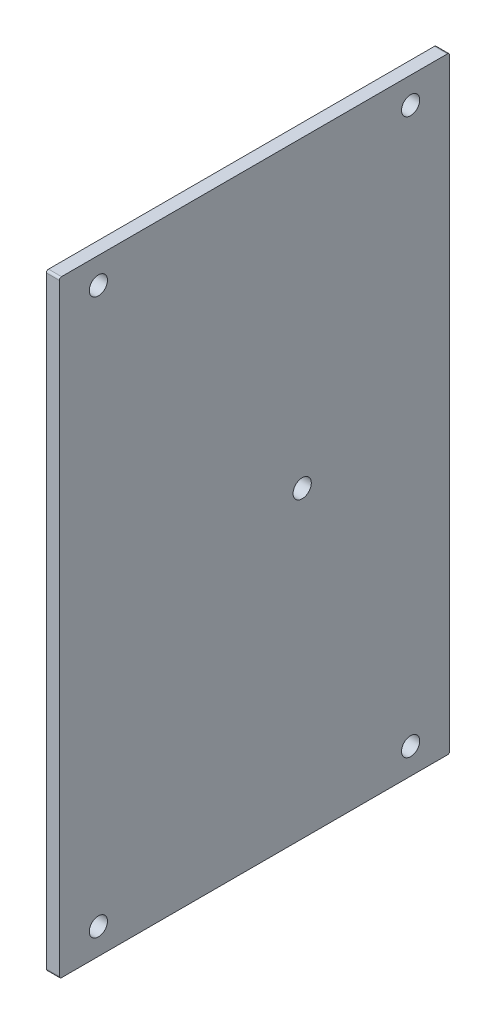
SolidWorks part; units mm, degrees
material "ABS"
ref_plane "Front Plane" through (0, 0, 0) normal (0, 0, 1) x (1, 0, 0)
ref_plane "Top Plane" through (0, 0, 0) normal (0, 1, 0) x (1, 0, 0)
ref_plane "Right Plane" through (0, 0, 0) normal (1, 0, 0) x (0, 0, -1)
sketch "Sketch1" plane through (0, 0, 0) normal (1, 0, 0) x (0, 0, -1)
  line L1 (0, 0) -> (90, 0)
  line L2 (0, 0) -> (0, -140)
  line L3 (0, -140) -> (90, -140)
  line L4 (90, 0) -> (90, -140)
  line L10 (45, 0) -> (45, -70) construction
  circle A0 centre (56, -70) radius 2.1
  circle A8 centre (9, -6) radius 2.1
  circle A9 centre (81, -6) radius 2.1
  circle A10 centre (81, -134) radius 2.1
  circle A11 centre (9, -134) radius 2.1
  point P21 (64.5, -93.5)
  point P26 (49.5, -93.5)
  point P29 (49.5, -85.5)
  dimension "D5" = 4.2
  dimension "D17" = 4.2
  dimension "D3" = 70
  dimension "D14" = 90
  dimension "D2" = 140
  dimension "D15" = 9
  dimension "D16" = 6
  dimension "D4" = 34
extrude "Boss-Extrude1" add sketch "Sketch1" along normal blind 3
fillet "Fillet1" radius 0.5 4 edges at (1.5, -140, -90) (1.5, -140, 0) (1.5, 0, -90) (1.5, 0, 0)
equation "\"Depth\"= 90mm"
equation "\"Height\"= 140mm"
equation "\"Width\"= 64mm"
equation "\"D14@Sketch1\"=\"Depth\""
equation "\"D2@Sketch1\"=\"Height\""
